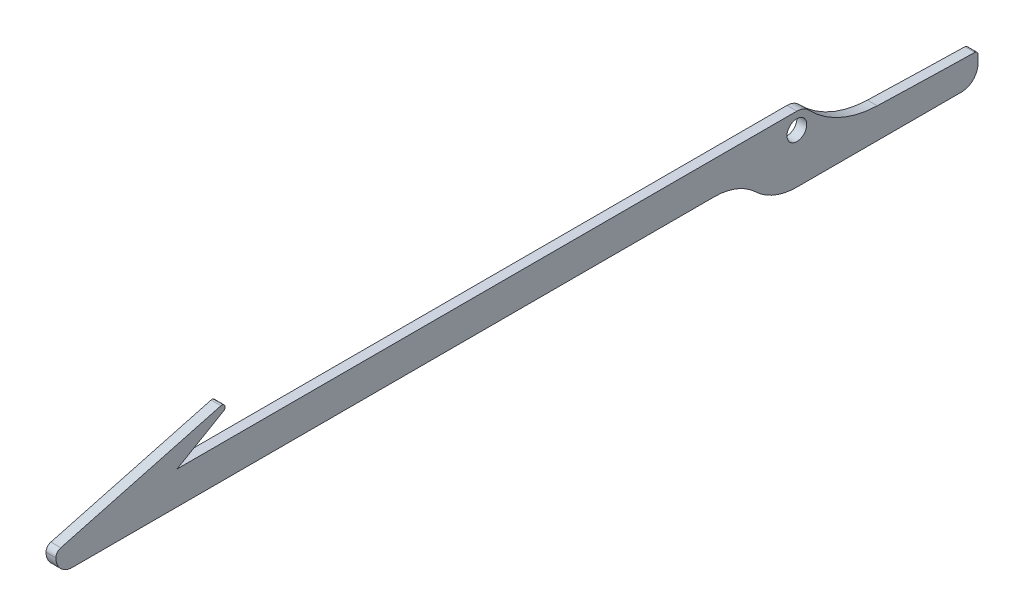
SolidWorks part; units mm, degrees
material "A2017"
ref_plane "正面" through (0, 0, 0) normal (0, 0, 1) x (1, 0, 0)
ref_plane "平面" through (0, 0, 0) normal (0, 1, 0) x (1, 0, 0)
ref_plane "右側面" through (0, 0, 0) normal (1, 0, 0) x (0, 0, -1)
sketch "ｽｹｯﾁ1" plane through (0, 0, 0) normal (1, 0, 0) x (0, 0, -1)
  line L0 (0, 0) -> (-220, 0) construction
  line L1 (0, -5) -> (-220, -5)
  line L2 (0, 5) -> (-220, 5)
  arc A0 (0, -5) -> (0, 5) centre (0, 0) ccw
  arc A1 (-220, 5) -> (-220, -5) centre (-220, 0) ccw
  point P3 (-110, 0)
  point P8 (-225, 0)
  dimension "D1" = 10
  dimension "D2" = 225
extrude "ﾎﾞｽ - 押し出し1" add sketch "ｽｹｯﾁ1" along normal mid plane 3
sketch "ｽｹｯﾁ2" plane through (1.5, 0, 0) normal (1, 0, 0) x (0, 0, -1)
  line L0 (-223.5176, 1.9319) -> (-174.8738, 14.9659)
  line L1 (-225, 0) -> (-151.1505, 0) construction
  line L2 (-174.115, 13.134) -> (-196.8637, 0)
  line L3 (-196.8637, 0) -> (-225, 0)
  line L4 (-174.615, 15) -> (-174.615, 0) construction
  arc A1 (-225, 0) -> (-223.5176, 1.9319) centre (-223, 0) cw
  arc A2 (-220, 5) -> (-220, -5) centre (-220, 0) ccw construction
  arc A3 (-174.8738, 14.9659) -> (-174.115, 13.134) centre (-174.615, 14) cw
  dimension "D2" = 2
  dimension "D3" = 1
  dimension "D1" = 15
  dimension "D4" = 30
  dimension "D5" = 15
extrude "ﾎﾞｽ - 押し出し2" add sketch "ｽｹｯﾁ2" against normal up to surface (3 mm away) up to face at (-1.5, 0, 110)
sketch "ｽｹｯﾁ3" plane through (1.5, 0, 0) normal (1, 0, 0) x (0, 0, -1)
  line L0 (-212.0672, 5) -> (-220, 5) construction
  line L1 (-212.0672, 5) -> (-220, 5)
  line L3 (-174.8738, 14.9659) -> (-223.5176, 1.9319)
  line L4 (-196.8637, 0) -> (-174.115, 13.134)
  line L5 (-225, 0) -> (-196.8637, 0)
  line L6 (-174.8738, 14.9659) -> (-223.5176, 1.9319)
  line L7 (-196.8637, 0) -> (-174.115, 13.134)
  line L8 (-225, 0) -> (-196.8637, 0)
  arc A0 (-220, 5) -> (-220, -5) centre (-220, 0) ccw construction
  arc A1 (-220, 5) -> (-220, -5) centre (-220, 0) ccw
  arc A2 (-174.115, 13.134) -> (-174.8738, 14.9659) centre (-174.615, 14) ccw
  arc A3 (-223.5176, 1.9319) -> (-225, 0) centre (-223, 0) ccw
  arc A4 (-174.115, 13.134) -> (-174.8738, 14.9659) centre (-174.615, 14) ccw
  arc A5 (-223.5176, 1.9319) -> (-225, 0) centre (-223, 0) ccw
  arc M6 (-220, 5) -> (-220, -5) centre (-220, 0) ccw
  line M13 (-212.0672, 5) -> (-220, 5)
  dimension "D1" = 0
extrude "ｶｯﾄ - 押し出し1" cut sketch "ｽｹｯﾁ3" against normal through all contours A5 L6 M13 M6 region at (1.5, 3.7672, 219.8125)
sketch "ｽｹｯﾁ4" plane through (1.5, 0, 0) normal (1, 0, 0) x (0, 0, -1)
  line L0 (-220, -5) -> (0, -5) construction
  line L1 (-25, -5) -> (55, -5)
  line L2 (-25, -5) -> (-25, -15)
  line L3 (-25, -15) -> (55, -15)
  line L4 (55, -5) -> (55, -15)
  dimension "D1" = 25
  dimension "D2" = 10
  dimension "D3" = 80
extrude "ﾎﾞｽ - 押し出し3" add sketch "ｽｹｯﾁ4" against normal up to surface (3 mm away) up to face at (-1.5, 3.6976, 150.1588)
sketch "ｽｹｯﾁ5" plane through (1.5, 0, 0) normal (1, 0, 0) x (0, 0, -1)
  line L0 (0, 0) -> (275, 0) construction
  line L1 (137.5, 0) -> (137.5, -7.5) construction
  line L2 (55, -15) -> (55, -5) construction
  line L3 (55, -5) -> (0, -5) construction
  line L4 (55, -15) -> (55, -5)
  line L5 (55, -5) -> (0, -5)
  circle A0 centre (0, 0) radius 5 construction
  circle A1 centre (275, 0) radius 5 construction
  arc A2 (-0.1818, -4.9967) -> (275.1818, -4.9967) centre (137.5, 3780) ccw
  arc A3 (0, -5) -> (-0.1818, -4.9967) centre (0, 0) cw
  line M10 (55, -5) -> (0, -5)
  dimension "D1" = 275
  dimension "D2" = 15
extrude "ｶｯﾄ - 押し出し2" cut sketch "ｽｹｯﾁ5" against normal through all contours A3 A2 L4 M10 region at (1.5, -5.5575, -35.9286)
fillet "ﾌｨﾚｯﾄ1" radius 5 1 edges at (0, -15, -55)
fillet "ﾌｨﾚｯﾄ2" radius 30 1 edges at (0, -4.9967, 0.1818)
fillet "ﾌｨﾚｯﾄ3" radius 1 1 edges at (0, -6.6014, -55)
sketch "ｽｹｯﾁ6" plane through (1.5, 0, 0) normal (1, 0, 0) x (0, 0, -1)
  line L0 (-25, -15) -> (50, -15) construction
  line L1 (-220, -5) -> (-25, -5) construction
  line L2 (0, -15) -> (-25, -15)
  line L3 (-25, -15) -> (-25, -5)
  line L4 (0, 0) -> (0, -15) construction
  arc A0 (-25, -5) -> (-12.5, -10) centre (-25, -23.125) cw
  arc A1 (-12.5, -10) -> (0, -15) centre (0, 3.125) ccw
extrude "ｶｯﾄ - 押し出し3" cut sketch "ｽｹｯﾁ6" against normal through all
sketch "ｽｹｯﾁ7" plane through (1.5, 0, 0) normal (1, 0, 0) x (0, 0, -1)
  circle A0 centre (0, 0) radius 3
  dimension "D1" = 6
extrude "ｶｯﾄ - 押し出し4" cut sketch "ｽｹｯﾁ7" against normal through all
